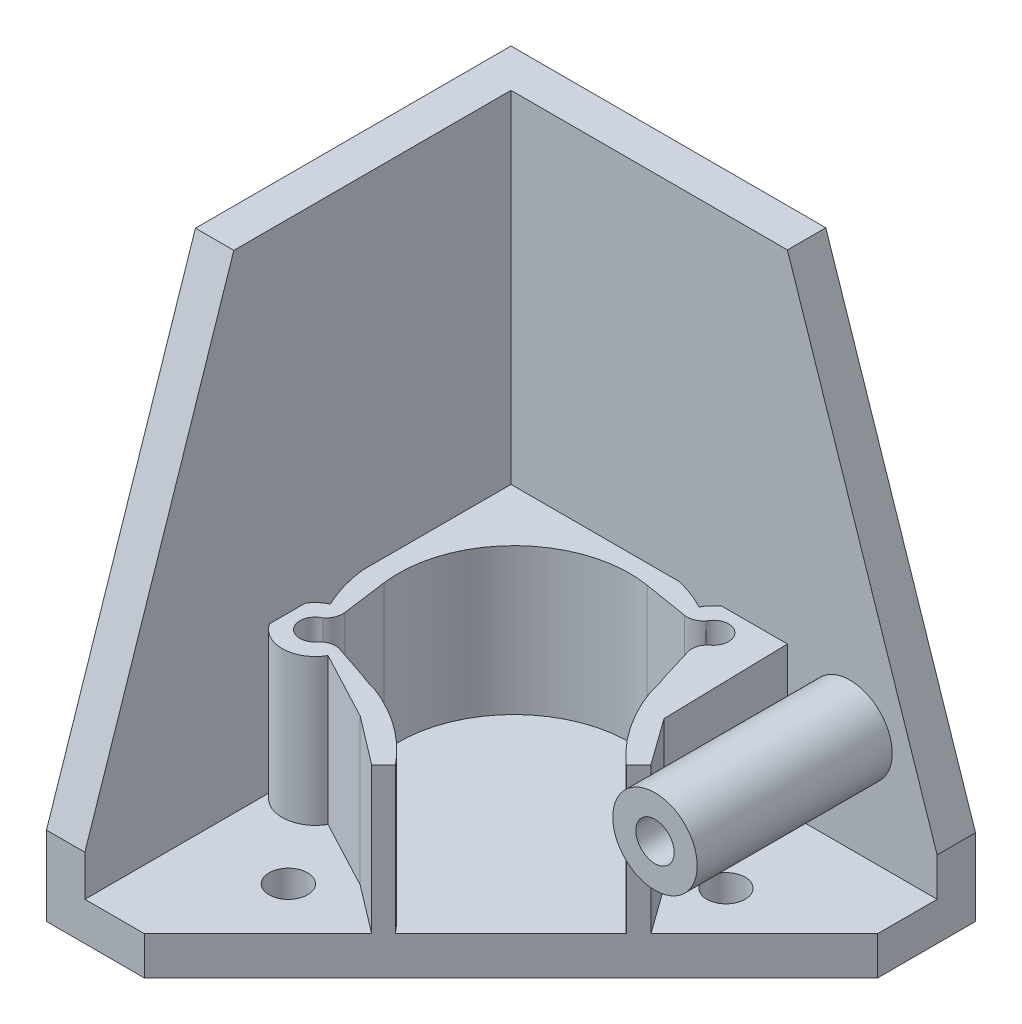
SolidWorks part; units mm, degrees
ref_plane "Front" through (0, 0, 0) normal (0, 0, 1) x (1, 0, 0)
ref_plane "Top" through (0, 0, 0) normal (0, 1, 0) x (1, 0, 0)
ref_plane "Right" through (0, 0, 0) normal (1, 0, 0) x (0, 0, -1)
sketch "Sketch1" plane through (0, 0, 0) normal (0, 1, 0) x (1, 0, 0)
  line L0 (0, 0) -> (0, 60.5)
  line L1 (0, -55) -> (0, 55) construction
  line L2 (0, 60.5) -> (60.5, 60.5)
  line L3 (60.5, 60.5) -> (60.5, 47.75)
  line L4 (60.5, 47.75) -> (12.75, 0)
  line L5 (-55, 0) -> (55, 0) construction
  line L6 (12.75, 0) -> (0, 0)
  dimension "D1" = 60.5
  dimension "D2" = 12.75
extrude "Boss-Extrude1" add sketch "Sketch1" along normal blind 5
sketch "Sketch4" plane through (0, 0, 0) normal (-1, 0, 0) x (0, 0, 1)
  line L0 (-60.5, 5) -> (-60.5, 68.5)
  line L1 (-60.5, 68.5) -> (-19.4, 68.5)
  line L2 (-19.4, 68.5) -> (0, 10.3086)
  line L3 (0, 10.3086) -> (0, 5)
  line L4 (0, -2.75) -> (0, 2.75) construction
  line L5 (-60.5, 5) -> (0, 5) construction
  line L6 (-60.5, 5) -> (0, 5)
  dimension "D1" = 63.5
  dimension "D2" = 41.1
  dimension "D3" = 61.34
extrude "Boss-Extrude2" add sketch "Sketch4" against normal blind 5
sketch "Sketch5" plane through (0, 0, -60.5) normal (0, 0, -1) x (-1, 0, 0)
  line L0 (0, 68.5) -> (-41, 68.5)
  line L1 (-41, 68.5) -> (-60.5, 10.0047)
  line L2 (-60.5, 10.0047) -> (-60.5, 5)
  line L6 (-60.5, 0) -> (0, 0)
  line L7 (0, 0) -> (0, 68.5)
  line L8 (0, 68.5) -> (-5, 68.5)
  line L9 (-5, 68.5) -> (-5, 5)
  line L10 (-5, 5) -> (-60.5, 5)
  line L11 (-60.5, 5) -> (-60.5, 0)
  line L12 (-60.5, 0) -> (0, 0)
  line L13 (0, 0) -> (0, 68.5)
  line L14 (0, 68.5) -> (-5, 68.5)
  line L15 (-5, 68.5) -> (-5, 5)
  line L16 (-5, 5) -> (-60.5, 5)
  line L17 (-60.5, 5) -> (-60.5, 0)
  line M13 (-5, 68.5) -> (-5, 5)
  line M14 (-5, 5) -> (-60.5, 5)
  dimension "D2" = 41
  dimension "D3" = 61.66
  dimension "D1" = 0
extrude "Boss-Extrude3" add sketch "Sketch5" against normal blind 5 contours L1 L2 L0 M14 M13 region at (28.6471, 34.3845, -60.5)
sketch "Sketch6" plane through (0, 5, 0) normal (0, 1, 0) x (1, 0, 0)
  line L0 (60.5, 60.5) -> (0, 60.5) construction
  line L4 (0, 19.4) -> (0, 0)
  line L5 (60.5, 55.5) -> (5, 55.5)
  line L6 (5, 55.5) -> (5, 0)
  line L7 (5, 0) -> (12.75, 0)
  line L8 (12.75, 0) -> (60.5, 47.75)
  line L9 (60.5, 47.75) -> (60.5, 55.5)
  line L10 (60.5, 55.5) -> (5, 55.5)
  line L11 (5, 55.5) -> (5, 0)
  line L12 (5, 0) -> (12.75, 0)
  line L13 (12.75, 0) -> (60.5, 47.75)
  line L14 (60.5, 47.75) -> (60.5, 55.5)
  line L15 (0, 0) -> (5, 0)
  line L16 (5, 0) -> (5, 19.4)
  line L17 (5, 19.4) -> (0, 19.4)
  line L18 (0, 19.4) -> (0, 0)
  line L19 (0, 0) -> (5, 0)
  line L20 (5, 0) -> (5, 19.4)
  line L21 (5, 19.4) -> (0, 19.4)
  line L24 (0, 60.5) -> (0, 19.4)
  line L25 (0, 19.4) -> (5, 19.4)
  line L26 (5, 19.4) -> (5, 55.5)
  line L27 (5, 55.5) -> (41, 55.5)
  line L28 (41, 55.5) -> (41, 60.5)
  line L29 (41, 60.5) -> (0, 60.5)
  line L30 (0, 60.5) -> (0, 19.4)
  line L31 (0, 19.4) -> (5, 19.4)
  line L32 (5, 19.4) -> (5, 55.5)
  line L33 (5, 55.5) -> (41, 55.5)
  line L34 (41, 55.5) -> (41, 60.5)
  line L35 (41, 60.5) -> (0, 60.5)
  circle A0 centre (16.5, 15) radius 2.5
  circle A1 centre (45.5, 43) radius 2.5
  dimension "D1" = 5
  dimension "D2" = 5
  dimension "D3" = 0
  dimension "D4" = 15
  dimension "D6" = 16.5
  dimension "D7" = 15
  dimension "D9" = 17.5
  dimension "D5" = 0
  dimension "D8" = 0
extrude "Cut-Extrude1" cut sketch "Sketch6" against normal through all contours A0 | A1 region at (16.5, 5, -15) region at (45.5, 5, -43)
sketch "Sketch7" plane through (0, 5, 0) normal (0, 1, 0) x (1, 0, 0)
  line L0 (12.75, 0) -> (60.5, 47.75) construction
  line L1 (0, -33.275) -> (0, 33.275) construction
  line L2 (22.75, 38.1428) -> (36.625, 23.875) construction
  line L3 (27.5503, 14.8003) -> (21.3192, 19.5434)
  line L4 (21.3192, 19.5434) -> (12.3846, 24.2829)
  line L5 (36.625, 23.875) -> (9.463, 51.8061) construction
  line L6 (45.9495, 32.6929) -> (41.3821, 39.0539)
  line L7 (41.3821, 39.0539) -> (36.8938, 48.1173)
  line L8 (12.75, 0) -> (60.5, 47.75)
  line L9 (7.8273, 36.1137) -> (8.6247, 30.2498)
  line L10 (16.8588, 24.2829) -> (12.3846, 25.7746)
  line L11 (36.769, 43.6449) -> (35.4027, 48.1589)
  line L12 (25.1949, 53.0031) -> (31.0343, 52.0424)
  line L13 (41.3821, 39.0539) -> (41, 55.5)
  circle A0 centre (22.75, 38.1428) radius 15.06
  arc A1 (16.8588, 24.2829) -> (29.1015, 16.3515) centre (10.721, 1.3943) cw
  arc A2 (36.769, 43.6449) -> (44.3556, 31.1856) centre (59.82, 49.1414) ccw
  circle A3 centre (8.6247, 26.3793) radius 2
  circle A5 centre (34.9033, 51.9343) radius 2
  arc A6 (12.3846, 24.2829) -> (6.7403, 30.2498) centre (8.6247, 26.3793) cw
  arc A7 (6.7403, 30.2498) -> (31.0869, 53.926) centre (22.75, 38.1428) cw
  arc A8 (36.8938, 48.1173) -> (31.0869, 53.926) centre (34.9033, 51.9343) ccw
  arc A9 (8.6247, 30.2498) -> (7.8014, 28.2019) centre (6.4139, 29.9492) cw
  arc A10 (12.3846, 25.7746) -> (10.0999, 25.0288) centre (11.7459, 23.8589) ccw
  arc A11 (31.0343, 52.0424) -> (33.1043, 52.8082) centre (31.3965, 54.2439) ccw
  arc A12 (35.4027, 48.1589) -> (36.2121, 50.422) centre (37.3356, 48.7439) cw
  point P0 (22.75, 38.1428)
  line M5 (60.5, 55.5) -> (5, 55.5)
  line M6 (5, 55.5) -> (5, 0)
  line M8 (12.75, 0) -> (60.5, 47.75)
  dimension "D3" = 30.12
  dimension "D4" = 4
  dimension "D6" = 21.57
  dimension "D1" = 19.9
  dimension "D2" = 22.75
extrude "Boss-Extrude4" add sketch "Sketch7" along normal blind 19.05 contours L7 A8 A7 A6 L4 L3 A1 A0 A2 L6 A5 A3 M5 M6 M8 | A7 M6 M5 | A8 L7 L13 M5 region at (24.7836, 5, -17.6301) region at (39.7929, 5, -48.3078) region at (8.5465, 5, -51.66)
sketch "Sketch9" plane through (0, 0, -55.5) normal (0, 0, 1) x (1, 0, 0)
  line L0 (41, 5) -> (60.5, 5) construction
  line L1 (41, 5) -> (60.5, 5)
  line L2 (44.1312, 24.05) -> (37.5012, 24.05) construction
  line L3 (44.1312, 24.05) -> (37.5012, 24.05)
  line L5 (0, 0) -> (60.5, 0)
  line L6 (0, 68.5) -> (0, 0)
  line L7 (41, 68.5) -> (0, 68.5)
  line L8 (60.5, 10.0047) -> (41, 68.5)
  line L9 (60.5, 0) -> (60.5, 10.0047)
  line L10 (0, 0) -> (60.5, 0)
  line L11 (0, 68.5) -> (0, 0)
  line L12 (41, 68.5) -> (0, 68.5)
  line L13 (60.5, 10.0047) -> (41, 68.5)
  line L14 (60.5, 0) -> (60.5, 10.0047)
  circle A0 centre (49.1523, 18.55) radius 5.5
  circle A1 centre (49.1523, 18.55) radius 2.5
  point P12 (48.2176, 13.9456)
  point P13 (48.8407, 15)
  dimension "D2" = 5
  dimension "D3" = 3
  dimension "D1" = 0
extrude "Boss-Extrude5" add sketch "Sketch9" along normal blind 25.4 contours A0 A1 region at (43.8079, 18.55, -55.5)
sketch "Sketch12" plane through (0, 0, -55.5) normal (0, 0, 1) x (1, 0, 0)
  line L11 (5, 24.05) -> (26.9142, 24.05)
  line L12 (26.9142, 24.05) -> (26.9142, 5)
  line L13 (26.9142, 5) -> (32.4913, 5)
  line L14 (32.4913, 5) -> (32.4913, 24.05)
  line L15 (32.4913, 24.05) -> (41, 24.05)
  line L16 (41, 24.05) -> (41, 5)
  line L17 (41, 5) -> (60.5, 5)
  line L18 (60.5, 5) -> (60.5, 10.0047)
  line L19 (60.5, 10.0047) -> (41, 68.5)
  line L20 (41, 68.5) -> (5, 68.5)
  line L21 (5, 68.5) -> (5, 24.05)
  line L22 (5, 24.05) -> (26.9142, 24.05)
  line L23 (26.9142, 24.05) -> (26.9142, 5)
  line L24 (26.9142, 5) -> (32.4913, 5)
  line L25 (32.4913, 5) -> (32.4913, 24.05)
  line L26 (32.4913, 24.05) -> (41, 24.05)
  line L27 (41, 24.05) -> (41, 5)
  line L28 (41, 5) -> (60.5, 5)
  line L29 (60.5, 5) -> (60.5, 10.0047)
  line L30 (60.5, 10.0047) -> (41, 68.5)
  line L31 (41, 68.5) -> (5, 68.5)
  line L32 (5, 68.5) -> (5, 24.05)
  circle A0 centre (49.1523, 18.55) radius 5.5 construction
  circle A1 centre (49.1523, 18.55) radius 5.5
  dimension "D1" = 0
